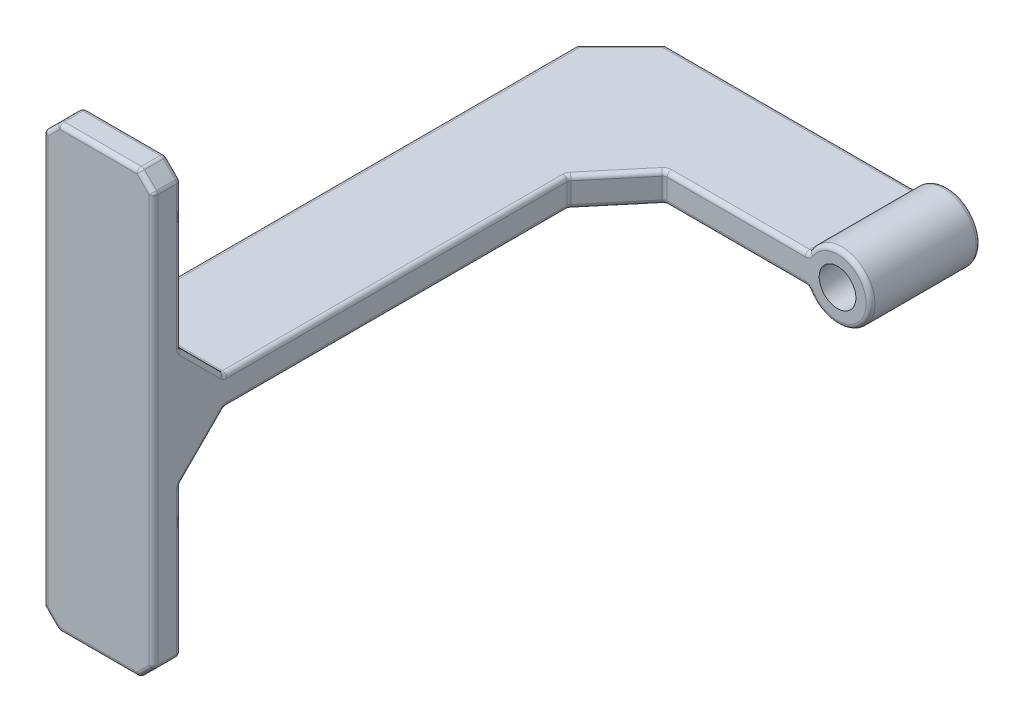
SolidWorks part; units mm, degrees
ref_plane "Front Plane" through (0, 0, 0) normal (0, 0, 1) x (1, 0, 0)
ref_plane "Top Plane" through (0, 0, 0) normal (0, 1, 0) x (1, 0, 0)
ref_plane "Right Plane" through (0, 0, 0) normal (1, 0, 0) x (0, 0, -1)
sketch "Sketch1" plane through (0, 0, 0) normal (0, 1, 0) x (1, 0, 0)
  line L0 (-25.7199, 0) -> (-25.7199, 95.25)
  line L1 (-25.7199, 95.25) -> (25.0801, 95.25)
  line L2 (25.0801, 95.25) -> (25.0801, 76.2)
  line L3 (25.0801, 76.2) -> (-6.6699, 76.2)
  line L4 (-6.6699, 76.2) -> (-6.6699, 0)
  line L5 (-6.6699, 0) -> (-25.7199, 0)
  dimension "D1" = 76.2
  dimension "D2" = 19.05
  dimension "D3" = 50.8
extrude "Boss-Extrude1" add sketch "Sketch1" along normal blind 2.54 and the other way blind 2.54
sketch "Sketch2" plane through (0, 0, 0) normal (0, 0, 1) x (1, 0, 0)
  line L0 (-6.6699, 0) -> (24.4679, 0) construction
  line L1 (-6.6699, 2.54) -> (-6.6699, -2.54) construction
  line L7 (-25.7199, 38.1) -> (-6.6699, 38.1)
  line L8 (-25.7199, 38.1) -> (-25.7199, -38.1)
  line L9 (-25.7199, -38.1) -> (-6.6699, -38.1)
  line L10 (-25.7199, -2.54) -> (-6.6699, -2.54)
  line L11 (-6.6699, -2.54) -> (-6.6699, 2.54)
  line L12 (-6.6699, 2.54) -> (-25.7199, 2.54)
  line L13 (-25.7199, 2.54) -> (-25.7199, -2.54)
  line L14 (-25.7199, -2.54) -> (-6.6699, -2.54) construction
  line L15 (-6.6699, -2.54) -> (-6.6699, 2.54) construction
  line L16 (-6.6699, 2.54) -> (-25.7199, 2.54) construction
  line L17 (-25.7199, 2.54) -> (-25.7199, -2.54) construction
  line L18 (-6.6699, 38.1) -> (-6.6699, -38.1)
  dimension "D2" = 76.2
  dimension "D1" = 0
extrude "Boss-Extrude2" add sketch "Sketch2" along normal blind 4.7625
chamfer "Chamfer1" distance 7.62 angle 45 2 edges at (-16.1949, 2.54, 0) (-16.1949, -2.54, 0)
sketch "Sketch3" plane through (0, 0, 0) normal (0, 1, 0) x (1, 0, 0)
  line L0 (25.0801, 76.2) -> (25.0801, 95.25)
  line L1 (25.0801, 76.2) -> (25.0801, 95.25)
  line L2 (27.6201, 76.2) -> (27.6201, 95.25)
  line L3 (25.0801, 76.2) -> (27.6201, 76.2)
  line L4 (25.0801, 95.25) -> (27.6201, 95.25)
  line L5 (30.7951, 76.2) -> (30.7951, 95.25) construction
  dimension "D1" = 2.54
  dimension "D2" = 3.175
revolve "Revolve1" add sketch "Sketch3" angle 360 about L5
sketch "Sketch4" plane through (25.0801, 0, 0) normal (1, 0, 0) x (0, 0, -1)
  line L4 (95.25, -2.54) -> (95.25, 2.54)
  line L5 (95.25, 2.54) -> (76.2, 2.54)
  line L6 (76.2, 2.54) -> (76.2, -2.54)
  line L7 (76.2, -2.54) -> (95.25, -2.54)
  line L8 (95.25, -2.54) -> (95.25, 2.54)
  line L9 (95.25, 2.54) -> (76.2, 2.54)
  line L10 (76.2, 2.54) -> (76.2, -2.54)
  line L11 (76.2, -2.54) -> (95.25, -2.54)
  dimension "D1" = 0
extrude "Boss-Extrude3" add sketch "Sketch4" along normal up to surface (0.5955 mm away) up to face at (36.5101, 0, -76.2)
chamfer "Chamfer2" distance 7.62 angle 45 1 edges at (-25.7199, 0, -95.25)
chamfer "Chamfer3" distance 7.62 angle 50 1 edges at (-6.6699, 0, -76.2) first distance on face at (12.2115, 0, -76.2)
chamfer "Chamfer4" distance 2.54 angle 45 4 edges at (-6.6699, 38.1, 2.3813) (-25.7199, 38.1, 2.3813) (-25.7199, -38.1, 2.3813) (-6.6699, -38.1, 2.3813)
fillet "Fillet2" radius 0.762 54 edges at (-9.2099, -38.1, 2.3813) (-7.9399, -36.83, 4.7625) (-16.1949, -38.1, 4.7625) (-16.1949, -38.1, 0) (-23.1799, -38.1, 2.3813) (-6.6699, -35.56, 2.3813) (-7.9399, -36.83, 0) (-7.9399, 36.83, 4.7625) (-6.6699, 0, 4.7625) (-24.4499, -36.83, 4.7625) (-16.1949, 38.1, 4.7625) (-9.2099, 38.1, 2.3813) (-25.7199, -35.56, 2.3813) (-24.4499, -36.83, 0) (-6.6699, -22.86, 0) (-6.6699, 35.56, 2.3813) (-7.9399, 36.83, 0) (-25.7199, 0, 4.7625) (-24.4499, 36.83, 4.7625) (-23.1799, 38.1, 2.3813) (-16.1949, 38.1, 0) (-16.1949, -10.16, 0) (-25.7199, -22.86, 0) (-6.6699, -6.35, -3.81) (-6.6699, 22.86, 0) (-25.7199, 35.56, 2.3813) (-24.4499, 36.83, 0) (-6.6699, -2.54, -37.3694) (-25.7199, -6.35, -3.81) (-16.1949, -2.54, -7.62) (-6.6699, 6.35, -3.81) (-16.1949, 10.16, 0) (-25.7199, 22.86, 0) (-6.6699, 2.54, -37.3694) (-6.6699, 0, -67.1188) (-2.8599, -2.54, -71.6594) (-25.7199, -2.54, -47.625) (-16.1949, 2.54, -7.62) (-25.7199, 6.35, -3.81) (0.9501, 0, -76.2) (-2.8599, 2.54, -71.6594) (13.3128, -2.54, -76.2) (-21.9099, -2.54, -91.44) (-25.7199, 0, -87.63) (-25.7199, 2.54, -47.625) (36.5101, 0, -76.2) (13.3128, 2.54, -76.2) (25.6756, -2.54, -85.725) (3.7878, -2.54, -95.25) (-18.0999, 0, -95.25) (-21.9099, 2.54, -91.44) (25.6756, 2.54, -85.725) (36.5101, 0, -95.25) (3.7878, 2.54, -95.25)
